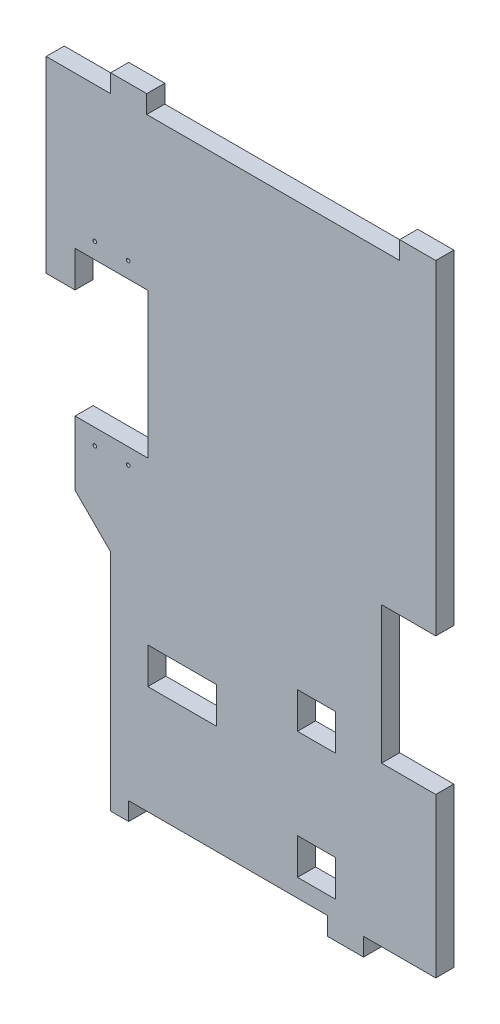
SolidWorks part; units mm, degrees
material "Balsa"
ref_plane "Plan de face" through (0, 0, 0) normal (0, 0, 1) x (1, 0, 0)
ref_plane "Plan de dessus" through (0, 0, 0) normal (0, 1, 0) x (1, 0, 0)
ref_plane "Plan de droite" through (0, 0, 0) normal (1, 0, 0) x (0, 0, -1)
sketch "Esquisse1" plane through (0, 0, 0) normal (0, 0, 1) x (1, 0, 0)
  line L0 (90, 82) -> (90, 167)
  line L1 (5, 0) -> (60, 0)
  line L2 (0, 0) -> (0, 167)
  line L3 (10, 167) -> (80, 167)
  line L4 (90, 0) -> (90, 44)
  line L5 (90, 82) -> (75, 82)
  line L6 (0, 167) -> (0, 172)
  line L7 (0, 172) -> (10, 172)
  line L8 (10, 167) -> (10, 172)
  line L9 (0, 0) -> (0, -5)
  line L10 (90, 167) -> (90, 172)
  line L11 (90, 172) -> (80, 172)
  line L12 (80, 167) -> (80, 172)
  line L13 (0, -5) -> (5, -5)
  line L14 (5, 0) -> (5, -5)
  line L16 (90, 44) -> (75, 44)
  line L17 (75, 82) -> (75, 44)
  line L18 (51.7344, 50) -> (62.2003, 50)
  line L19 (51.7344, 50) -> (51.7344, 40)
  line L20 (51.7344, 40) -> (62.2003, 40)
  line L25 (62.2003, 50) -> (62.2003, 40)
  line L32 (51.7344, 15) -> (62.2003, 15)
  line L34 (51.7344, 15) -> (51.7344, 5)
  line L35 (51.7344, 5) -> (62.2003, 5)
  line L37 (62.2003, 15) -> (62.2003, 5)
  line L54 (29.3073, 40) -> (10.2917, 40)
  line L55 (29.3073, 40) -> (29.3073, 30)
  line L56 (29.3073, 30) -> (10.2917, 30)
  line L57 (10.2917, 40) -> (10.2917, 30)
  line L58 (70, 0) -> (90, 0)
  line L60 (60, 0) -> (60, -5)
  line L61 (60, -5) -> (70, -5)
  line L62 (70, 0) -> (70, -5)
  dimension "D1" = 167
  dimension "D2" = 90
  dimension "D3" = 10
  dimension "D4" = 5
  dimension "D5" = 5
  dimension "D6" = 15
  dimension "D7" = 38
  dimension "D8" = 82
  dimension "D11" = 10
  dimension "D12" = 20
extrude "Boss.-Extru.1" add sketch "Esquisse1" along normal blind 5
sketch "Esquisse2" plane through (0, 0, 5) normal (0, 0, 1) x (1, 0, 0)
  line L0 (0, 172) -> (0, -5) construction
  line L1 (0, 167) -> (-9.8347, 167)
  line L2 (0, 167) -> (0, 57.1653)
  line L3 (0, 57.1653) -> (-9.8347, 67)
  line L4 (-9.8347, 167) -> (-9.8347, 67)
  line L6 (80, 167) -> (10, 167) construction
  dimension "D1" = 9.8347
  dimension "D2" = 135
  dimension "D3" = 100
extrude "Boss.-Extru.2" add sketch "Esquisse2" against normal blind 5
sketch "Esquisse3" plane through (0, 0, 0) normal (0, 0, -1) x (-1, 0, 0)
  line L0 (9.8347, 167) -> (9.8347, 67) construction
  line L1 (-10.3653, 125) -> (9.8347, 125)
  line L2 (-10.3653, 125) -> (-10.3653, 84.8)
  line L3 (-10.3653, 84.8) -> (9.8347, 84.8)
  line L4 (9.8347, 125) -> (9.8347, 84.8)
  line L5 (0, 167) -> (9.8347, 167) construction
  line L6 (4.3597, 129.4) -> (-4.8903, 129.4) construction
  line L7 (-4.8903, 129.4) -> (-4.8903, 80.4) construction
  line L8 (-4.8903, 80.4) -> (4.3597, 80.4) construction
  line L9 (9.8347, 167) -> (9.8347, 67) construction
  line L10 (-80, 167) -> (-10, 167) construction
  circle A0 centre (4.3597, 129.4) radius 0.5
  circle A1 centre (-4.8903, 129.4) radius 0.5
  circle A2 centre (4.3597, 80.4) radius 0.5
  circle A3 centre (-4.8903, 80.4) radius 0.5
  dimension "D9" = 1
  dimension "D1" = 17.8
  dimension "D2" = 42
  dimension "D3" = 20.2
  dimension "D4" = 9.25
  dimension "D5" = 9.25
  dimension "D6" = 49
  dimension "D7" = 14.725
  dimension "D8" = 37.6
extrude "Enlèv. mat.-Extru.1" cut sketch "Esquisse3" against normal blind 5
sketch "Esquisse4" plane through (0, 0, 5) normal (0, 0, 1) x (1, 0, 0)
  line L0 (-9.8347, 167) -> (-17.8347, 167)
  line L1 (-9.8347, 167) -> (-9.8347, 125) construction
  line L2 (-17.8347, 167) -> (-17.8347, 115)
  line L3 (-17.8347, 115) -> (-9.8347, 115)
  line L4 (-9.8347, 115) -> (-9.8347, 125)
  line L5 (-9.8347, 125) -> (-9.8347, 167)
  line L6 (0, 167) -> (-9.8347, 167) construction
  dimension "D2" = 8
  dimension "D3" = 10
extrude "Boss.-Extru.3" add sketch "Esquisse4" against normal blind 5
